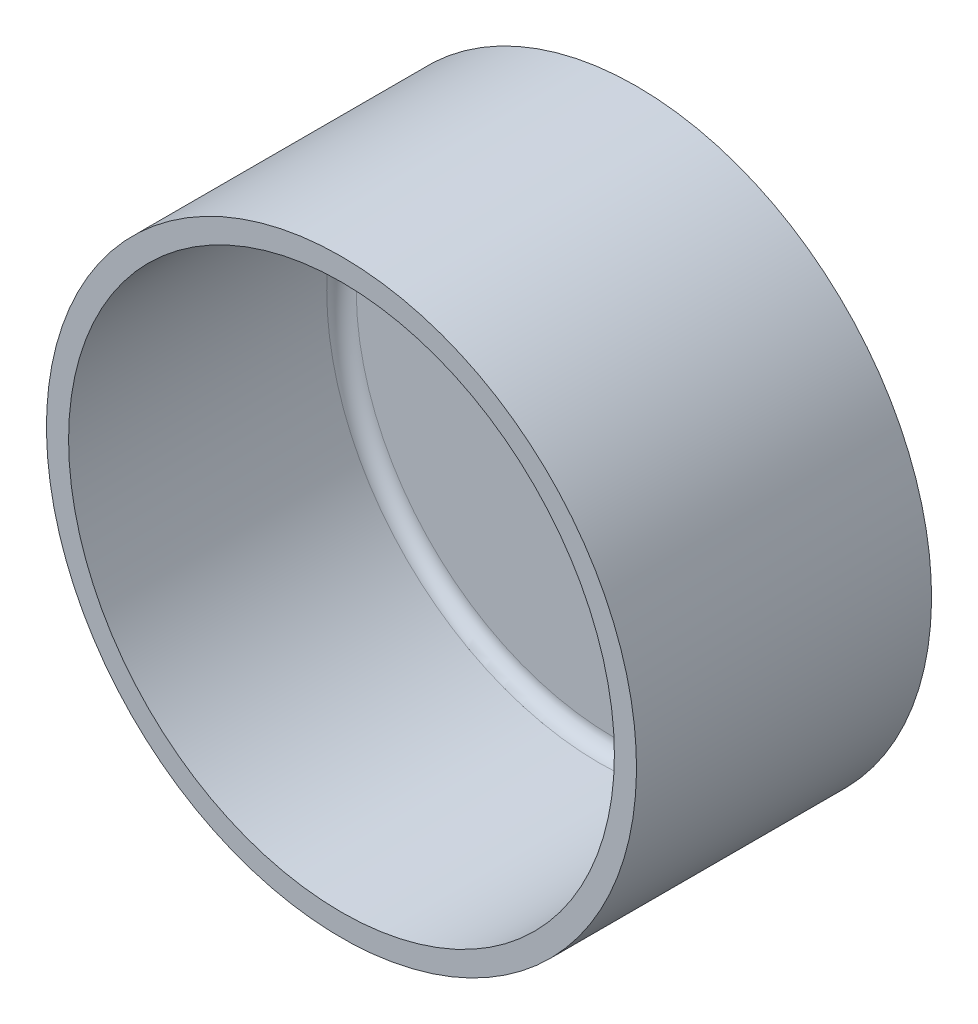
SolidWorks part; units mm, degrees
ref_plane "Front Plane" through (0, 0, 0) normal (0, 0, 1) x (1, 0, 0)
ref_plane "Top Plane" through (0, 0, 0) normal (0, 1, 0) x (1, 0, 0)
ref_plane "Right Plane" through (0, 0, 0) normal (1, 0, 0) x (0, 0, -1)
sketch "Sketch1" plane through (0, 0, 0) normal (0, 0, 1) x (1, 0, 0)
  circle A0 centre (0, 0) radius 10
  circle A1 centre (0, 6) radius 2.65
  circle A2 centre (5.7063, 1.8541) radius 2.65
  circle A3 centre (3.5267, -4.8541) radius 2.65
  circle A4 centre (-3.5267, -4.8541) radius 2.65
  circle A5 centre (-5.7063, 1.8541) radius 2.65
  point P16 (0, 0)
  dimension "D1" = 5.3
  dimension "D2" = 20
  dimension "D3" = 6
  dimension "D4" = 5
extrude "Boss-Extrude1" add sketch "Sketch1" along normal blind 1
sketch "Sketch2" plane through (0, 0, 1) normal (0, 0, 1) x (1, 0, 0)
  circle A0 centre (0, 0) radius 10
ref_plane "Plane1" through (0, 0, 45) normal (0, 0, 1) x (1, 0, 0)
sketch "Sketch3" plane through (0, 0, 45) normal (0, 0, 1) x (1, 0, 0)
  circle A0 centre (0, 0) radius 30
  dimension "D1" = 60
ref_plane "Plane2" through (0, 0, 15) normal (0, 0, 1) x (1, 0, 0)
sketch "Sketch4" plane through (0, 0, 15) normal (0, 0, 1) x (1, 0, 0)
  circle A0 centre (0, 0) radius 20
  dimension "D1" = 40
loft "Loft-Thin1" add profiles "Sketch2", "Sketch4", "Sketch3" parameters "D1"=1
sketch "Sketch5" plane through (0, 0, 0) normal (0, 0, -1) x (-1, 0, 0)
  circle A0 centre (0, 0) radius 10
  circle A1 centre (0, 0) radius 11.5
  dimension "D1" = 1.5
extrude "Boss-Extrude2" add sketch "Sketch5" against normal blind 1
sketch "Sketch8" plane through (0, 0, 0) normal (1, 0, 0) x (0, 0, -1)
  line L0 (0, 18.5) -> (18.5, 18.5)
  line L1 (18.5, 18.5) -> (18.5, 0)
  line L2 (0, 20) -> (20, 20)
  line L3 (20, 20) -> (20, 0)
  line L4 (20, 0) -> (18.5, 0)
  line L5 (0, 18.5) -> (0, 20)
  dimension "D2" = 20
  dimension "D3" = 20
  dimension "D1" = 1.5
revolve "Revolve1" add sketch "Sketch8" angle 360 about L4
sketch "Sketch10" plane through (0, 0, 0) normal (0, 0, 1) x (1, 0, 0)
  circle A0 centre (0, 0) radius 51.0166
extrude "Cut-Extrude2" cut sketch "Sketch10" along normal blind 70
fillet "Fillet1" radius 1 1 edges at (0, 18.5, -18.5)
sketch "Sketch12" plane through (0, 0, -18.5) normal (0, 0, 1) x (1, 0, 0)
  circle A0 centre (0, 5) radius 1
  circle A1 centre (0, -5) radius 1
  circle A2 centre (0, 0) radius 1.5
  dimension "D1" = 2
  dimension "D2" = 2
  dimension "D4" = 3
  dimension "D3" = 10
extrude "Cut-Extrude4" cut sketch "Sketch12" against normal blind 10
